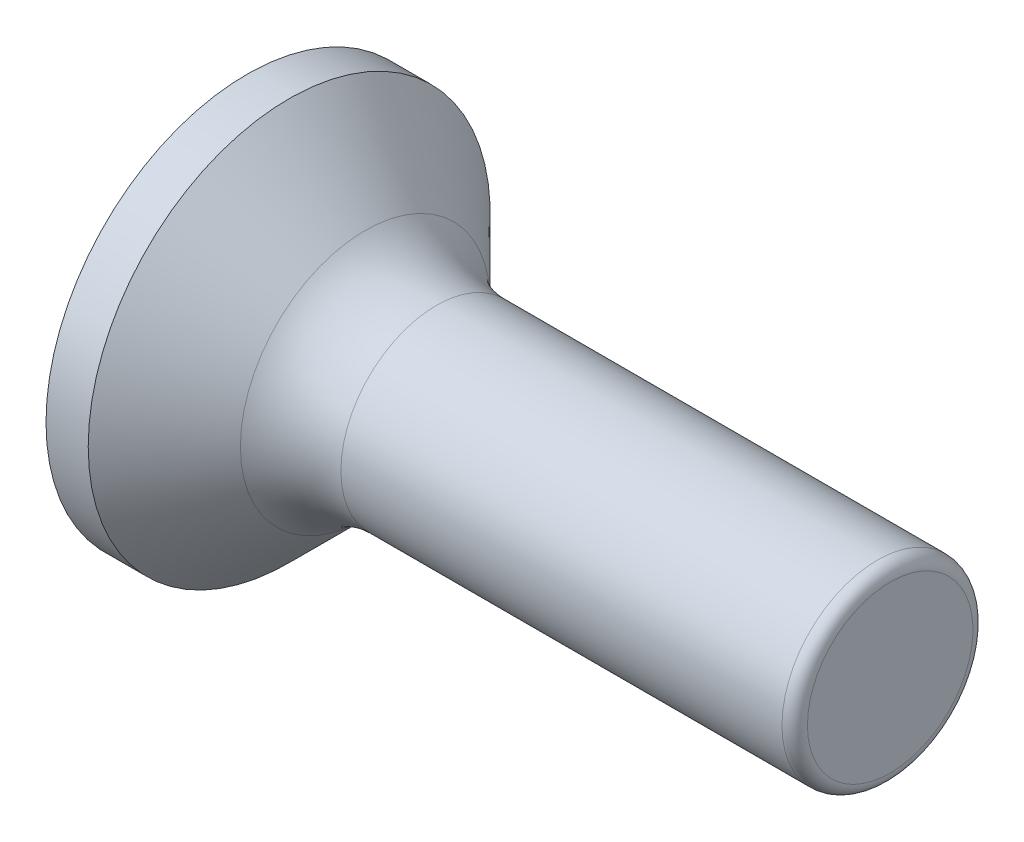
SolidWorks part; units mm, degrees
ref_plane "Front" through (0, 0, 0) normal (0, 0, 1) x (1, 0, 0)
ref_plane "Top" through (0, 0, 0) normal (0, 1, 0) x (1, 0, 0)
ref_plane "Right" through (0, 0, 0) normal (1, 0, 0) x (0, 0, -1)
sketch "Sketch1" plane through (0, 0, 0) normal (0, 0, 1) x (1, 0, 0)
  line L0 (-11.6961, 0) -> (11.3165, 0) construction
  line L1 (32, 0) -> (32, 4.75)
  line L2 (32, 4.75) -> (9.4211, 4.75)
  line L4 (2.1, 10) -> (0, 10)
  line L5 (32, 0) -> (0, 0)
  line L6 (5.8855, 6.2145) -> (2.1, 10)
  line L7 (0, 10) -> (0, 0)
  arc A0 (5.8855, 6.2145) -> (9.4211, 4.75) centre (9.4211, 9.75) ccw
  dimension "D1" = 45
  dimension "l" = 32
  dimension "k" = 5.8855
revolve "Base" add sketch "Sketch1" angle 360 about L0
cosmetic thread "ThreadCosmetic1" [suppressed] parameters "D1"=20.6835, "D2"=7.6
sketch "Sketch2" plane through (0, 0, 0) normal (1, 0, 0) x (0, 0, -1)
  line L0 (-6.8682, 0) -> (7.6314, 0) construction
  line L1 (0, 6.2457) -> (0, -5.6834) construction
  line L2 (1, 5) -> (-1, 5)
  line L3 (-1, 5) -> (-1, 1)
  line L4 (-1, 1) -> (-5, 1)
  line L5 (-5, 1) -> (-5, -1)
  line L6 (-1, -1) -> (-5, -1)
  line L7 (-1, -5) -> (-1, -1)
  line L8 (1, -5) -> (-1, -5)
  line L9 (1, -5) -> (1, -1)
  line L10 (1, -1) -> (5, -1)
  line L11 (5, 1) -> (5, -1)
  line L12 (1, 1) -> (5, 1)
  line L13 (1, 5) -> (1, 1)
  point P5 (5, 0)
  point P11 (-5, 0)
  point P15 (0, -5)
  point P20 (0, 5)
  dimension "D1" = 2
extrude "Cut-Extrude1" cut sketch "Sketch2" along normal blind 2.9428
draft "Draft1" type of draft neutral plane draft angle 30 faces to draft 4 face at (1.4714, 0, -5) face at (1.4714, 0, 5) face at (1.4714, -5, 0) face at (1.4714, 5, 0) neutral plane through (0, 10, 0) neutral plane normal (-1, 0, 0) parameters "D1"=30
fillet "Fillet1" radius 0.6333 1 edges at (32, 0, 4.75)
sketch "Sketch3" plane through (0, 0, 0) normal (0, 0, 1) x (1, 0, 0)
  line L0 (10.8415, 5.7) -> (11.7915, 5.7)
  line L1 (11.7915, 5.7) -> (11.7915, 4.75)
  line L2 (11.7915, 4.75) -> (11.3165, 3.9273)
  line L3 (11.3165, 3.9273) -> (10.8415, 4.75)
  line L4 (10.8415, 4.75) -> (10.8415, 5.7)
  line L5 (0, 0) -> (8.0438, 0) construction
  line L6 (5.8855, 6.2145) -> (5.8855, -6.2145) construction
  dimension "D1" = 9.5
  dimension "D2" = 0.95
  dimension "D3" = 5.4309
revolve "Cut-Revolve10" [suppressed] cut sketch "Sketch3" angle 360 about L5
pattern_linear "LPattern10" [suppressed] count 18 spacing 1.14 along (1, 0, 0) of bodies 103
equation "\"D2@ThreadCosmetic1\" = \"st@Sketch1\" * 4 / 5"
equation "\"D1@Sketch2\" = \"m@Sketch2\" / 5"
equation "\"qs@Cut-Extrude1\" = \"k@Sketch1\" / 2"
equation "\"D1@ThreadCosmetic1\" = \"l@Sketch1\" - \"k@Sketch1\"  - \"a@Sketch1\""
equation "\"D1@Fillet1\" = \"st@Sketch1\" / 15"
equation "\"D1@Sketch3\" = \"st@Sketch1\""
equation "\"D2@Sketch3\" = (  \"st@Sketch1\" - \"D2@ThreadCosmetic1\" )  / 2"
equation "\"D3@Sketch3\" = \"a@Sketch1\""
equation "\"D3@LPattern10\" = \"D2@Sketch3\" * 1.2"
equation "\"D1@LPattern10\" = \"D1@ThreadCosmetic1\" / \"D3@LPattern10\""
